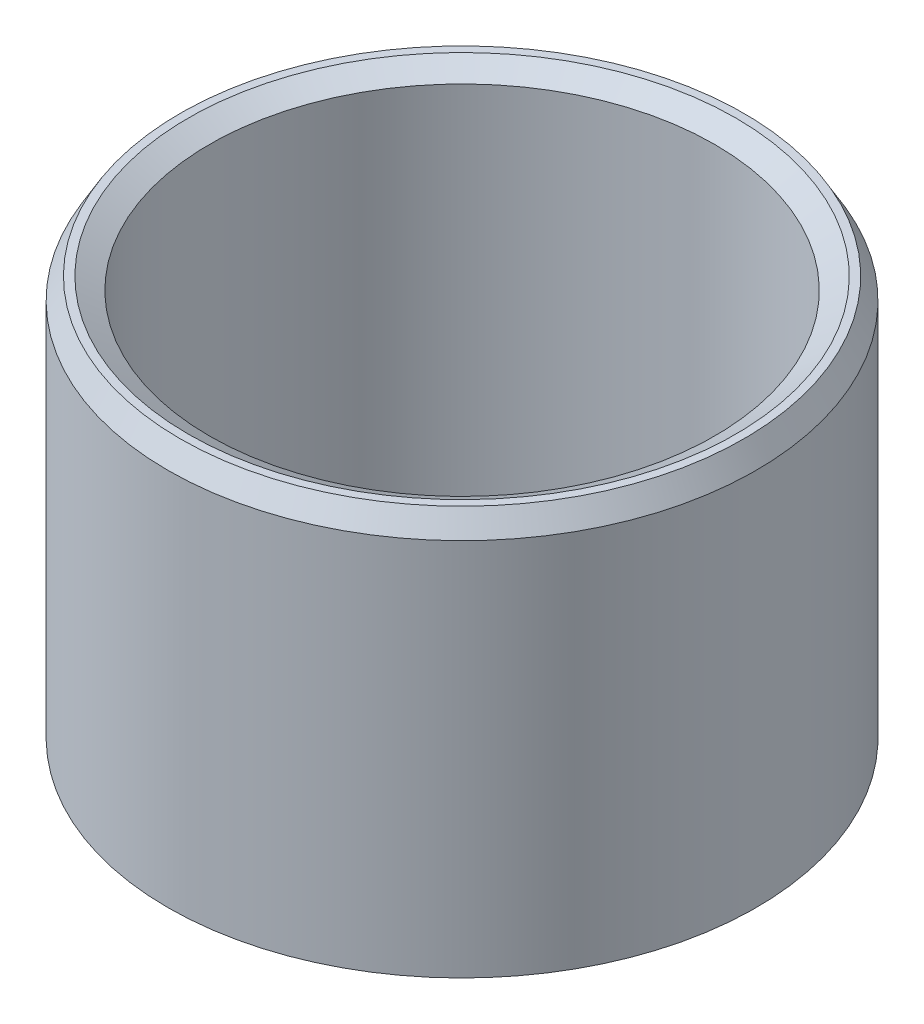
SolidWorks part; units mm, degrees
ref_plane "Front Plane" through (0, 0, 0) normal (0, 0, 1) x (1, 0, 0)
ref_plane "Top Plane" through (0, 0, 0) normal (0, 1, 0) x (1, 0, 0)
ref_plane "Right Plane" through (0, 0, 0) normal (1, 0, 0) x (0, 0, -1)
sketch "Sketch1" plane through (0, 0, 0) normal (0, 1, 0) x (1, 0, 0)
  circle A0 centre (0, 0) radius 35
  dimension "SLEEVE_OD" = 70
extrude "Boss-Extrude1" add sketch "Sketch1" along normal blind 49.0441
sketch "Sketch2" plane through (0, 0, 0) normal (0, 1, 0) x (1, 0, 0)
  circle A0 centre (0, 0) radius 30.0595
  dimension "BORE_D" = 60.1191
extrude "Cut-Extrude1" cut sketch "Sketch2" along normal through all
chamfer "Chamfer1" distance 2.5216 angle 30 4 edges at (0, 49.0441, 30.0595) (0, 0, 30.0595) (0, 0, 35) (0, 49.0441, 35) first distance on face at (0, 49.0441, 30.0595) first distance on face at (0, 0, 30.0595) first distance on face at (0, 49.0441, 35)
